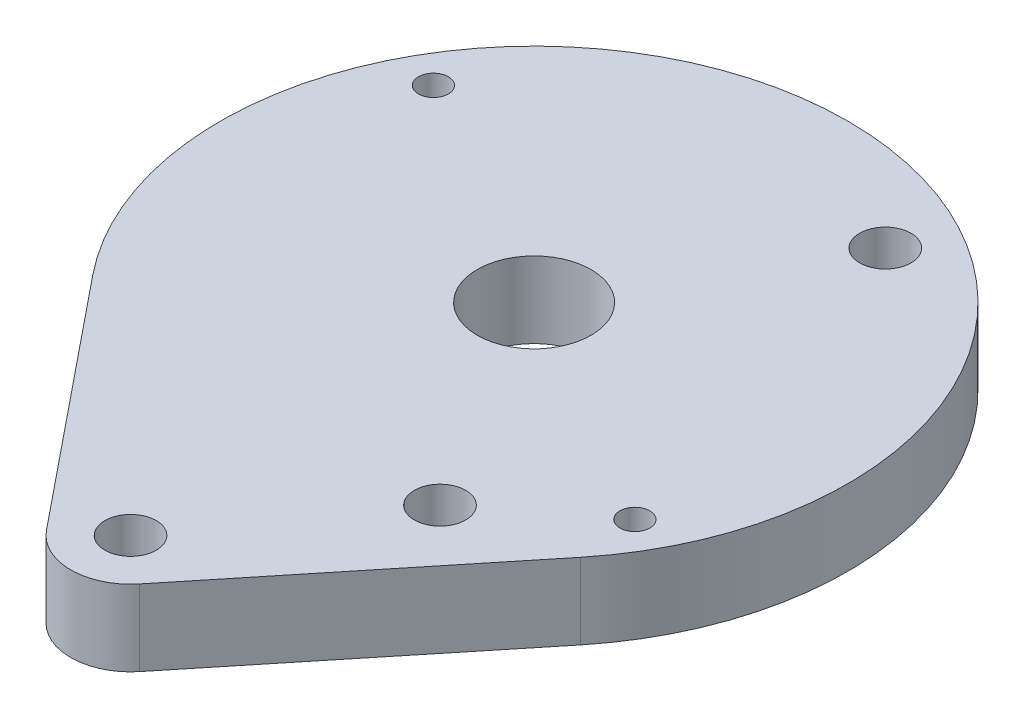
SolidWorks part; units mm, degrees
ref_plane "Front Plane" through (0, 0, 0) normal (0, 0, 1) x (1, 0, 0)
ref_plane "Top Plane" through (0, 0, 0) normal (0, 1, 0) x (1, 0, 0)
ref_plane "Right Plane" through (0, 0, 0) normal (1, 0, 0) x (0, 0, -1)
sketch "Sketch1" plane through (0, 0, 0) normal (0, 1, 0) x (1, 0, 0)
  line L0 (-20.3935, -16.5278) -> (-3.8845, -36.8981)
  line L1 (-26.25, 26.25) -> (26.25, 26.25) construction
  line L2 (-26.25, 26.25) -> (-26.25, -38.75) construction
  line L3 (-26.25, -38.75) -> (26.25, -38.75) construction
  line L4 (26.25, 26.25) -> (26.25, -38.75) construction
  line L5 (-26.25, 26.25) -> (26.25, -38.75) construction
  line L6 (-26.25, -38.75) -> (26.25, 26.25) construction
  line L8 (3.8845, -36.8981) -> (20.3935, -16.5278)
  circle A2 centre (0, 0) radius 4.7625
  circle A3 centre (0, 0) radius 26.25
  circle A4 centre (0, -33.75) radius 5
  point P4 (0, -6.25)
  point P5 (0, 0)
  dimension "D5" = 52.5
  dimension "D6" = 9.525
  dimension "D1" = 10
  dimension "D2" = 65
extrude "Boss-Extrude1" add sketch "Sketch1" along normal mid plane 6.35 contours L4 A3 L1 L2 L3 | A3 A2 | A4 region at (0, 0, 27.6054) region at (-23.0249, 0, -10.9767) region at (0, 0, 33.75)
hole_wizard "M4 Clearance Hole1" positions "Sketch6" profile "Sketch7" hole size "M4" standard "ANSI Metric" end condition up to next
sketch "Sketch6" plane through (0, 3.175, 0) normal (0, 1, 0) x (1, 0, 0)
  line L0 (0, 0) -> (10.75, 18.6195)
  line L1 (0, 0) -> (10.75, -18.6195)
  line L2 (0, 0) -> (-21.5, 0)
  point P2 (10.75, 18.6195)
  point P10 (10.75, -18.6195)
  point P169 (0, -33.75)
  point P171 (0, 0)
  point P174 (0, 0)
  point P175 (0, -29.655)
  point P176 (0, 0)
  dimension "D1" = 21.5
  dimension "D2" = 120
  dimension "D3" = 120
  dimension "D4" = 33.75
sketch "Sketch7" plane through (0, 3.175, 33.75) normal (1, 0, 0) x (0, 0, 1)
  line L0 (0, 0) -> (0, 6.35)
  line L1 (0, 6.35) -> (2.15, 6.35)
  line L2 (2.15, 6.35) -> (2.15, 0)
  line L5 (2.15, 0) -> (0, 0)
  line L11 (0, -6.35) -> (0, 107.95) construction
  dimension "Thru Hole Dia." = 4.3
  dimension "Thru Hole Depth" = 6.35
hole_wizard "M3x0.5 Tapped Hole1" positions "Sketch8" profile "Sketch9" tap size "M3x0.5" standard "ANSI Metric" end condition up to next
sketch "Sketch8" plane through (0, 3.175, 0) normal (0, 1, 0) x (1, 0, 0)
  line L0 (-19.9316, 11.5075) -> (19.9316, -11.5075) construction
  line L2 (-1000, 0) -> (49000, 0) construction
  point P2 (19.9316, -11.5075)
  point P17 (-19.9316, 11.5075)
  point P20 (0, 0)
  dimension "D1" = 46.03
  dimension "D2" = 30
sketch "Sketch9" plane through (19.9316, 3.175, 11.5075) normal (1, 0, 0) x (0, 0, 1)
  line L0 (0, 0) -> (0, 6.35)
  line L1 (0, 6.35) -> (1.25, 6.35)
  line L2 (1.25, 6.35) -> (1.25, 0)
  line L5 (1.25, 0) -> (0, 0)
  line L11 (0, -6.35) -> (0, 107.95) construction
  dimension "Thru Tap Drill Dia." = 2.5
  dimension "Thru Tap Drill Depth" = 6.35
cosmetic thread "Hole Thread1"
cosmetic thread "Hole Thread6"
